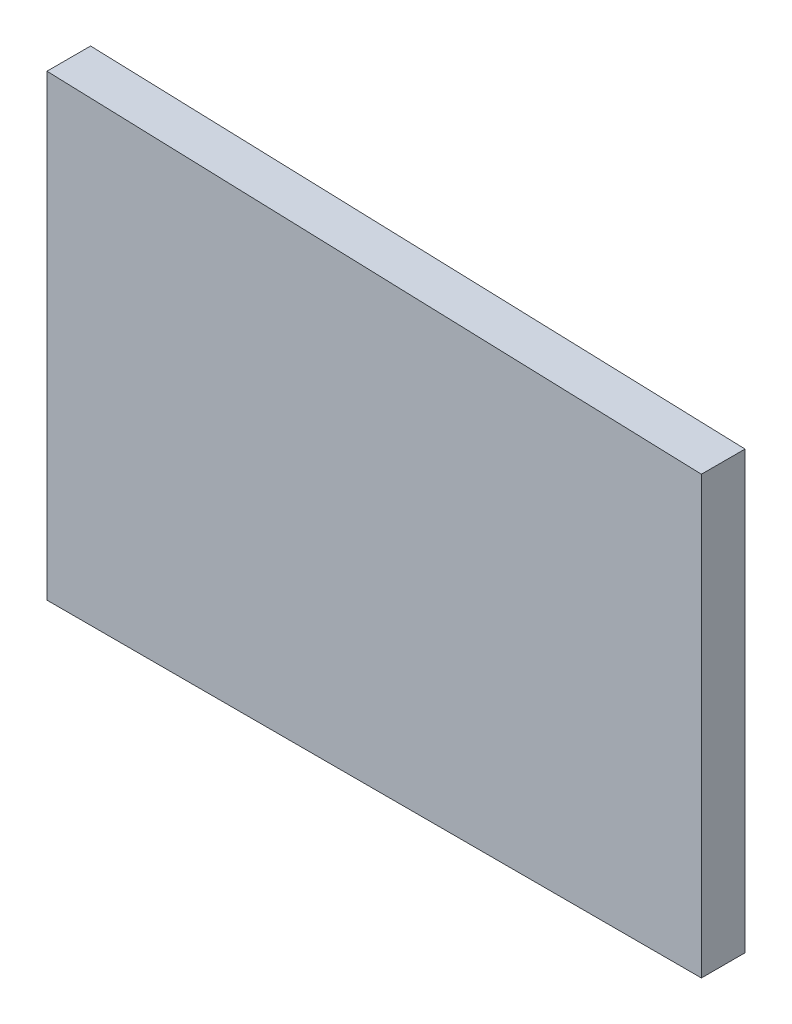
SolidWorks part; units mm, degrees
ref_plane "Ebene vorne" through (0, 0, 0) normal (0, 0, 1) x (1, 0, 0)
ref_plane "Ebene oben" through (0, 0, 0) normal (0, 1, 0) x (1, 0, 0)
ref_plane "Ebene rechts" through (0, 0, 0) normal (1, 0, 0) x (0, 0, -1)
sketch "Skizze1" plane through (0, 0, 0) normal (0, 0, 1) x (1, 0, 0)
  line L0 (0, 0) -> (0, 21)
  line L1 (0, 21) -> (30, 20)
  line L2 (30, 20) -> (30, 0)
  line L3 (30, 0) -> (0, 0)
  dimension "D1" = 30
  dimension "D2" = 20
  dimension "D3" = 21
  dimension "D4" = 90
  dimension "D5" = 90
extrude "Aufsatz-Linear austragen1" add sketch "Skizze1" along normal blind 2
sketch "Skizze4" plane through (0, 0, 0) normal (0, 0, 1) x (1, 0, 0)
  line L1 (0, 0) -> (30, 0)
  line L2 (0, 0) -> (0, 20)
  line L3 (0, 20) -> (30, 20)
  line L4 (30, 0) -> (30, 20)
  dimension "D1" = 30
  dimension "D2" = 20
sketch "Skizze2" plane through (0, 0, 2) normal (0, 0, 1) x (1, 0, 0)
  circle A0 centre (14.6667, 10.5) radius 18.0378
sketch "Skizze3" plane through (0, 0, 2) normal (0, 0, 1) x (1, 0, 0)
  line L0 (1, 1) -> (29, 1)
  line L1 (1, 1) -> (1, 19)
  line L2 (29, 1) -> (29, 19)
  line L3 (1, 19) -> (29, 19)
  line L4 (1, 1) -> (29, 19) construction
  line L5 (29, 1) -> (1, 19) construction
  line L6 (30, 0) -> (30, 20) construction
  line L7 (30, 20) -> (0, 21) construction
  point P1 (15, 10)
  point P8 (30, 10)
  point P11 (15, 20.5)
  dimension "D1" = 18
  dimension "D2" = 28
ref_point "SWASI_Vision_Point_1"
ref_point "SWASI_Vision_Point_1_helper"
ref_point "SWASI_Vision_Point_2"
ref_point "SWASI_Vision_Point_2_helper"
ref_point "SWASI_Vision_Point_3"
ref_point "SWASI_Vision_Point_3_helper"
ref_point "SWASI_Vision_Point_4"
ref_plane "SWASI_Alignment_Plane_1" through (0, 0, 0) normal (0, -1, 0) x (-1, 0, 0)
ref_plane "SWASI_Alignment_Plane_2ddasd" through (0, 0, 0) normal (0, 0, 1) x (1, 0, 0)
ref_axis "Achse1" through (30, 0, 2) along (-1, 0, 0)
ref_axis "Achse2" through (0, 0, 2) along (0.9978, 0, -0.0665)
ref_axis "Achse3" through (0, 0, 0) along (0.9978, 0, 0.0665)
ref_point "SWASI_Surface_Center_Point"
ref_axis "Achse5" through (0, 0, 2) along (0, 0, -1)
ref_axis "SWASI_Norm_Alignment_Plane_3" through (30, 0, 0) along (-1, 0, 0)
ref_plane "SWASI_Alignment_Plane_3" through (15, 0, 1) normal (-1, 0, 0) x (0, 0, 1)
ref_point "Punkt1"
ref_point "Punkt2"
